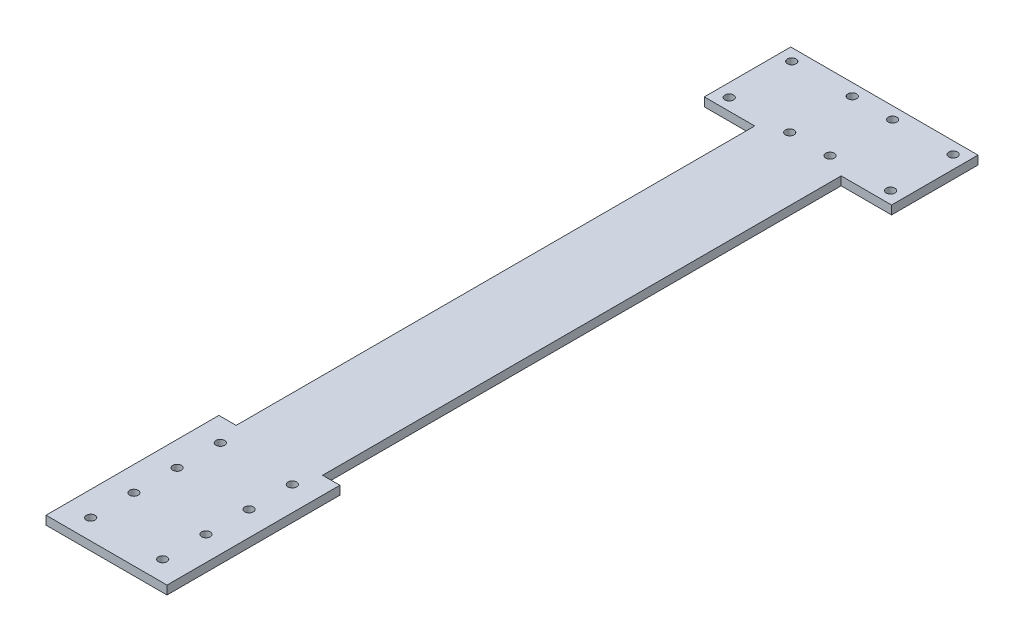
SolidWorks part; units mm, degrees
ref_plane "Front Plane" through (0, 0, 0) normal (0, 0, 1) x (1, 0, 0)
ref_plane "Top Plane" through (0, 0, 0) normal (0, 1, 0) x (1, 0, 0)
ref_plane "Right Plane" through (0, 0, 0) normal (1, 0, 0) x (0, 0, -1)
sketch "Sketch1" plane through (0, 0, 0) normal (0, 1, 0) x (1, 0, 0)
  line L0 (0, 0) -> (0, 270) construction
  line L1 (32.5, 270) -> (-32.5, 270)
  line L2 (-32.5, 270) -> (-32.5, 240)
  line L3 (-32.5, 240) -> (-15, 240)
  line L4 (-15, 240) -> (-15, 60)
  line L5 (-15, 60) -> (-21, 60)
  line L6 (-21, 60) -> (-21, 0)
  line L7 (-21, 0) -> (21, 0)
  line L8 (21, 60) -> (21, 0)
  line L9 (15, 60) -> (21, 60)
  line L10 (15, 240) -> (15, 60)
  line L11 (32.5, 240) -> (15, 240)
  line L12 (32.5, 270) -> (32.5, 240)
  dimension "D1" = 65
  dimension "D2" = 30
  dimension "D3" = 42
  dimension "D4" = 30
  dimension "D5" = 60
  dimension "D6" = 180
extrude "Boss-Extrude1" add sketch "Sketch1" along normal blind 3
sketch "Sketch2" plane through (0, 3, 0) normal (0, 1, 0) x (1, 0, 0)
  line L0 (0, 270) -> (0, 0) construction
  line L1 (32.5, 270) -> (-32.5, 270) construction
  line L2 (-28, 270) -> (-28, 244.15) construction
  line L3 (-7, 270) -> (-7, 244.15) construction
  line L4 (-28, 265.85) -> (-7, 265.85) construction
  line L5 (-17.5, 265.85) -> (-17.5, 130.7949) construction
  line L6 (-28, 255) -> (-7, 255) construction
  line L7 (-32.5, 255) -> (32.5, 255) construction
  line L8 (-32.5, 270) -> (-32.5, 240) construction
  line L9 (32.5, 240) -> (32.5, 270) construction
  circle A0 centre (-28, 265.85) radius 1.5
  circle A1 centre (-7, 265.85) radius 1.5
  circle A2 centre (-28, 244.15) radius 1.5
  circle A3 centre (-7, 244.15) radius 1.5
  dimension "D3" = 21.7
  dimension "D4" = 3
  dimension "D1" = 21
  dimension "D2" = 17.5
extrude "Cut-Extrude1" cut sketch "Sketch2" against normal through all both and the other way through all
mirror "Mirror1" about plane through (0, 0, 0) normal (1, 0, 0) of "Cut-Extrude1"
sketch "Sketch3" plane through (0, 3, 0) normal (0, 1, 0) x (1, 0, 0)
  line L0 (-12.5, 60) -> (-12.5, 0)
  line L1 (-15, 60) -> (-21, 60) construction
  line L2 (-21, 0) -> (21, 0) construction
  line L3 (0, 0) -> (0, 270) construction
  line L4 (32.5, 270) -> (-32.5, 270) construction
  circle A0 centre (-12.5, 52) radius 1.5
  circle A11 centre (12.5, 52) radius 1.5
  dimension "D1" = 3
  dimension "D2" = 25
  dimension "D3" = 8
extrude "Cut-Extrude2" cut sketch "Sketch3" against normal through all both and the other way through all contours L0 A0 | L0 A0 | A11 region at (-11.8634, 3, -52) region at (-13.1366, 3, -52) region at (12.5, 3, -52)
pattern_linear "LPattern1" count 4 spacing 15 along (0, 0, 1) of "Cut-Extrude2"
